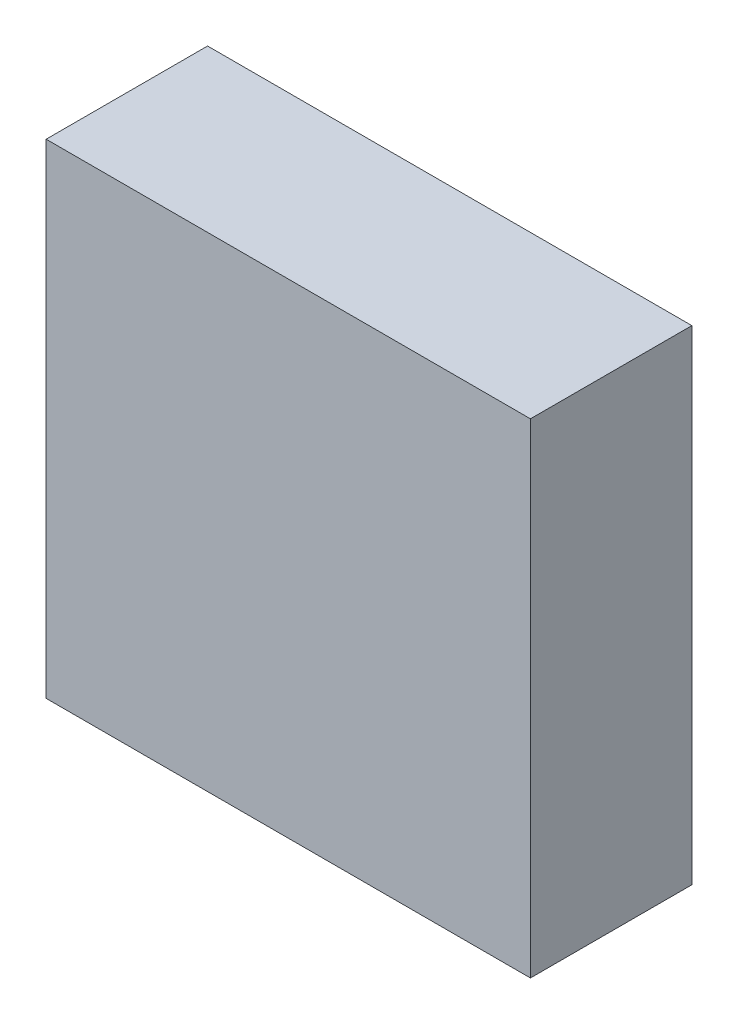
SolidWorks part; units mm, degrees
material "Plain Carbon Steel"
ref_plane "Front Plane" through (0, 0, 0) normal (0, 0, 1) x (1, 0, 0)
ref_plane "Top Plane" through (0, 0, 0) normal (0, 1, 0) x (1, 0, 0)
ref_plane "Right Plane" through (0, 0, 0) normal (1, 0, 0) x (0, 0, -1)
sketch "Sketch1" plane through (0, 0, 0) normal (0, 0, 1) x (1, 0, 0)
  line L1 (-15, -15) -> (15, -15)
  line L2 (-15, -15) -> (-15, 15)
  line L3 (-15, 15) -> (15, 15)
  line L4 (15, -15) -> (15, 15)
  line L5 (-15, -15) -> (15, 15) construction
  line L6 (-15, 15) -> (15, -15) construction
  point P0 (0, 0)
  dimension "D1" = 30
  dimension "D2" = 30
extrude "Boss-Extrude1" add sketch "Sketch1" along normal blind 10
